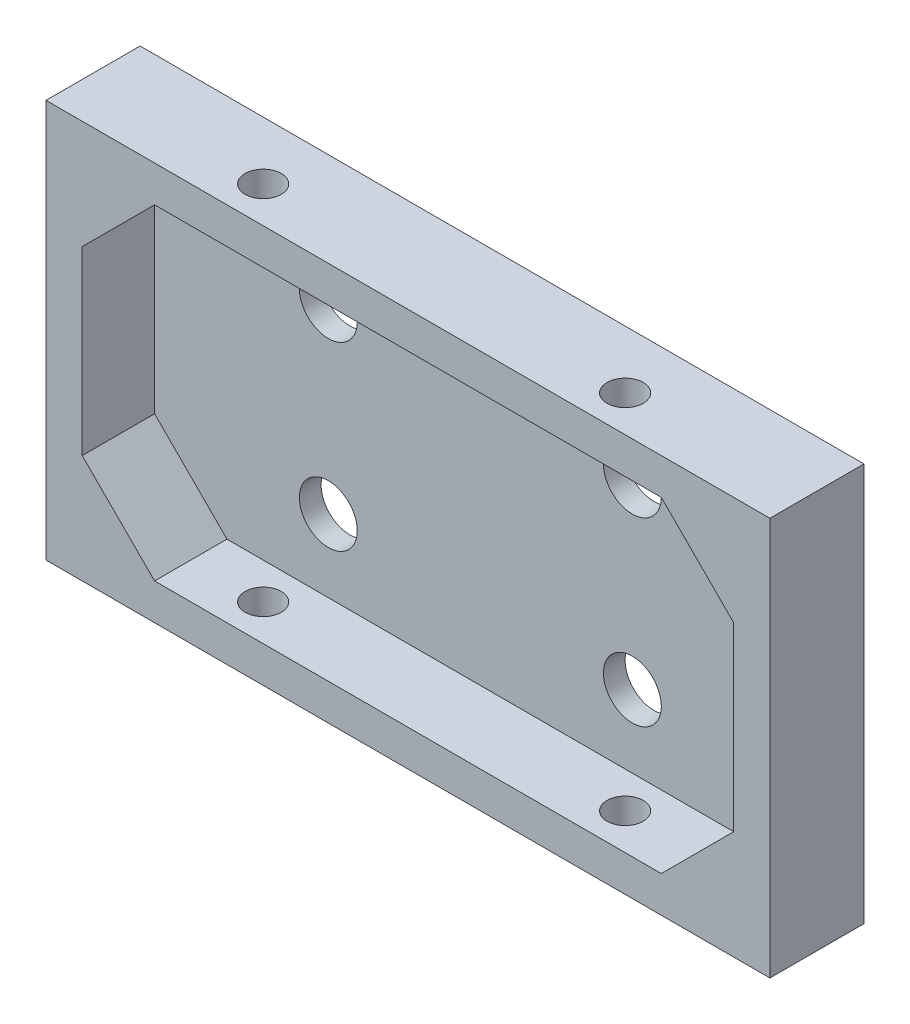
SolidWorks part; units mm, degrees
ref_plane "Plan de face" through (0, 0, 0) normal (0, 0, 1) x (1, 0, 0)
ref_plane "Plan de dessus" through (0, 0, 0) normal (0, 1, 0) x (1, 0, 0)
ref_plane "Plan de droite" through (0, 0, 0) normal (1, 0, 0) x (0, 0, -1)
sketch "Esquisse1" plane through (0, 0, 0) normal (0, 0, 1) x (1, 0, 0)
  line L0 (44.1184, 33.7284) -> (54.1184, 33.7284)
  line L1 (-45.8816, 33.7284) -> (44.1184, 33.7284)
  line L2 (-45.8816, 33.7284) -> (-45.8816, -21.2716)
  line L3 (-45.8816, -21.2716) -> (54.1184, -21.2716)
  line L4 (54.1184, 23.7284) -> (54.1184, -21.2716)
  line L5 (54.1184, 33.7284) -> (54.1184, 23.7284)
  point P6 (54.1184, 33.7284)
  dimension "D1" = 100
  dimension "D2" = 55
extrude "Boss.-Extru.1" add sketch "Esquisse1" along normal blind 13
shell "Coque1" thickness 5 removed face at (4.1184, 6.2284, 13)
sketch "Esquisse3" plane through (0, -21.2716, 0) normal (0, -1, 0) x (1, 0, 0)
  line L0 (-45.8816, 13) -> (54.1184, 13) construction
  line L2 (54.1184, 13) -> (54.1184, 0) construction
  line L3 (-45.8816, 13) -> (-45.8816, 0) construction
  circle A0 centre (-20.8816, 8) radius 2.5
  circle A1 centre (29.1184, 8) radius 2.5
  dimension "D1" = 5
  dimension "D2" = 5
  dimension "D3" = 5
  dimension "D4" = 5
  dimension "D5" = 25
  dimension "D6" = 25
extrude "Enlèv. mat.-Extru.2" cut sketch "Esquisse3" against normal up to surface (55 mm away) up to face at (4.1184, 33.7284, 6.5)
sketch "Esquisse4" plane through (0, 0, 3) normal (0, 0, 1) x (1, 0, 0)
  line L0 (-30.8816, 28.7284) -> (-40.8816, 18.7284)
  line L1 (49.1184, 28.7284) -> (-40.8816, 28.7284) construction
  line L2 (-40.8816, 28.7284) -> (-40.8816, -16.2716) construction
  line L3 (-40.8816, 18.7284) -> (-40.8816, 28.7284)
  line L4 (-40.8816, 28.7284) -> (-30.8816, 28.7284)
  line L5 (49.1184, 28.7284) -> (49.1184, 18.7284)
  line L6 (49.1184, -16.2716) -> (49.1184, 28.7284) construction
  line L7 (49.1184, 18.7284) -> (39.1184, 28.7284)
  line L8 (39.1184, 28.7284) -> (49.1184, 28.7284)
  line L9 (49.1184, 28.7284) -> (-40.8816, 28.7284) construction
  line L10 (49.1184, -16.2716) -> (49.1184, -6.2716)
  line L11 (49.1184, -6.2716) -> (39.1184, -16.2716)
  line L12 (-40.8816, -16.2716) -> (49.1184, -16.2716) construction
  line L13 (39.1184, -16.2716) -> (49.1184, -16.2716)
  line L14 (-30.8816, -16.2716) -> (-40.8816, -6.2716)
  line L15 (-40.8816, 28.7284) -> (-40.8816, -16.2716) construction
  line L16 (-40.8816, -6.2716) -> (-40.8816, -16.2716)
  line L17 (-40.8816, -16.2716) -> (-30.8816, -16.2716)
  dimension "D1" = 10
  dimension "D2" = 10
  dimension "D3" = 10
  dimension "D4" = 10
  dimension "D5" = 10
  dimension "D6" = 10
  dimension "D7" = 10
  dimension "D8" = 10
extrude "Boss.-Extru.2" add sketch "Esquisse4" along normal up to surface (10 mm away) up to face at (4.1184, 6.2284, 13)
sketch "Esquisse5" plane through (0, 0, 3) normal (0, 0, 1) x (1, 0, 0)
  line L0 (54.1184, 33.7284) -> (-45.8816, 33.7284) construction
  line L2 (-45.8816, 33.7284) -> (-45.8816, -21.2716) construction
  circle A0 centre (-16.8816, 18.7284) radius 4
  dimension "D1" = 8
  dimension "D4" = 15
  dimension "D6" = 29
extrude "Enlèv. mat.-Extru.3" cut sketch "Esquisse5" against normal up to surface (3 mm away) up to face at (4.1184, 6.2284, 0)
pattern_linear "Répétition linéaire1" count 2 spacing 42 along (1, 0, 0) count 2 spacing 25 along (0, -1, 0) of "Enlèv. mat.-Extru.3"
